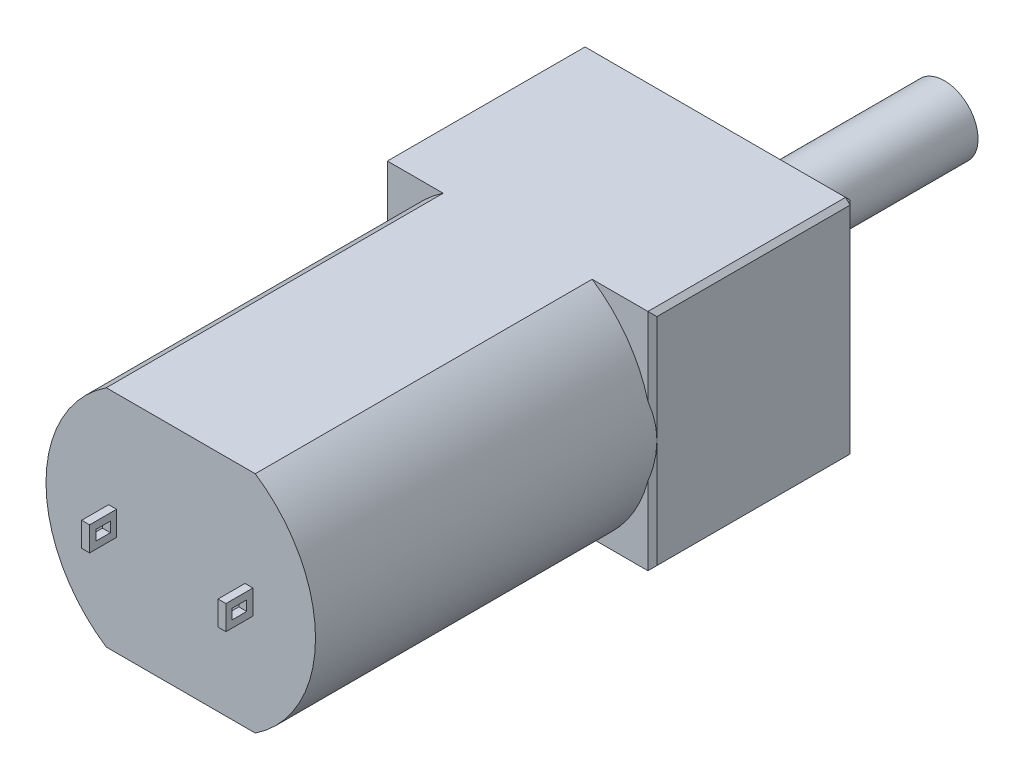
SolidWorks part; units mm, degrees
ref_plane "前视基准面" through (0, 0, 0) normal (0, 0, 1) x (1, 0, 0)
ref_plane "上视基准面" through (0, 0, 0) normal (0, 1, 0) x (1, 0, 0)
ref_plane "右视基准面" through (0, 0, 0) normal (1, 0, 0) x (0, 0, -1)
sketch "草图1" plane through (0, 0, 0) normal (0, 0, 1) x (1, 0, 0)
  line L1 (-6, -5) -> (6, -5)
  line L2 (-6, -5) -> (-6, 5)
  line L3 (-6, 5) -> (6, 5)
  line L4 (6, -5) -> (6, 5)
  line L5 (-6, -5) -> (6, 5) construction
  line L6 (-6, 5) -> (6, -5) construction
  point P0 (0, 0)
  dimension "D1" = 12
  dimension "D2" = 10
extrude "凸台-拉伸2" add sketch "草图1" along normal blind 9
sketch "草图2" plane through (0, 0, 9) normal (0, 0, 1) x (1, 0, 0)
  line L0 (-3.3166, 5) -> (3.3166, 5)
  line L1 (6, 5) -> (-6, 5) construction
  line L2 (-3.3166, -5) -> (3.3166, -5)
  arc A0 (-3.3166, 5) -> (-3.3166, -5) centre (0, 0) ccw
  arc A1 (3.3166, -5) -> (3.3166, 5) centre (0, 0) ccw
extrude "凸台-拉伸4" add sketch "草图2" along normal blind 15
chamfer "倒角4" distance 0.2 angle 45 12 edges at (6, -5, 4.5) (6, -2.5, 9) (6, 2.5, 9) (6, 5, 4.5) (6, 0, 0) (0, -5, 0) (0, 5, 0) (-6, -2.5, 9) (-6, 2.5, 9) (-6, 5, 4.5) (-6, 0, 0) (-6, -5, 4.5)
sketch "草图4" plane through (0, 0, 24) normal (0, 0, 1) x (1, 0, 0)
  line L0 (0, -5) -> (0, 5) construction
  line L1 (3.3166, 5) -> (-3.3166, 5) construction
  line L2 (0, 0) -> (3.0357, 0) construction
  line L3 (-2.8596, -0.5423) -> (-3.2119, -0.5423)
  line L4 (2.8596, 0.5423) -> (3.2119, 0.5423)
  line L5 (2.8596, 0.5423) -> (2.8596, -0.5423)
  line L6 (2.8596, -0.5423) -> (3.2119, -0.5423)
  line L7 (3.2119, 0.5423) -> (3.2119, -0.5423)
  line L8 (2.8596, 0.5423) -> (3.2119, -0.5423) construction
  line L9 (2.8596, -0.5423) -> (3.2119, 0.5423) construction
  line L10 (-3.2119, 0.5423) -> (-3.2119, -0.5423)
  line L11 (-2.8596, 0.5423) -> (-3.2119, 0.5423)
  line L12 (-2.8596, 0.5423) -> (-2.8596, -0.5423)
  line L13 (-2.8596, -0.5423) -> (-3.2119, 0.5423) construction
  line L14 (-2.8596, 0.5423) -> (-3.2119, -0.5423) construction
  point P6 (0, 0)
  point P17 (-3.0357, 0)
extrude "凸台-拉伸5" add sketch "草图4" along normal blind 1.2
sketch "草图5" plane through (3.2119, 0, 0) normal (1, 0, 0) x (0, 0, -1)
  line L0 (-24, 0) -> (-24.6, 0) construction
  line L1 (-24, 5) -> (-24, -5) construction
  line L3 (-24.275, -0.225) -> (-24.925, -0.225)
  line L4 (-24.275, -0.225) -> (-24.275, 0.225)
  line L5 (-24.275, 0.225) -> (-24.925, 0.225)
  line L6 (-24.925, -0.225) -> (-24.925, 0.225)
  line L7 (-24.275, -0.225) -> (-24.925, 0.225) construction
  line L8 (-24.275, 0.225) -> (-24.925, -0.225) construction
  dimension "D1" = 0.6
  dimension "D2" = 0.45
  dimension "D3" = 0.65
extrude "切除-拉伸1" cut sketch "草图5" against normal through all
sketch "草图6" plane through (0, 0, 0) normal (0, 0, -1) x (-1, 0, 0)
  circle A0 centre (0, 0) radius 1.5
  dimension "D1" = 3
extrude "凸台-拉伸6" add sketch "草图6" along normal blind 10
